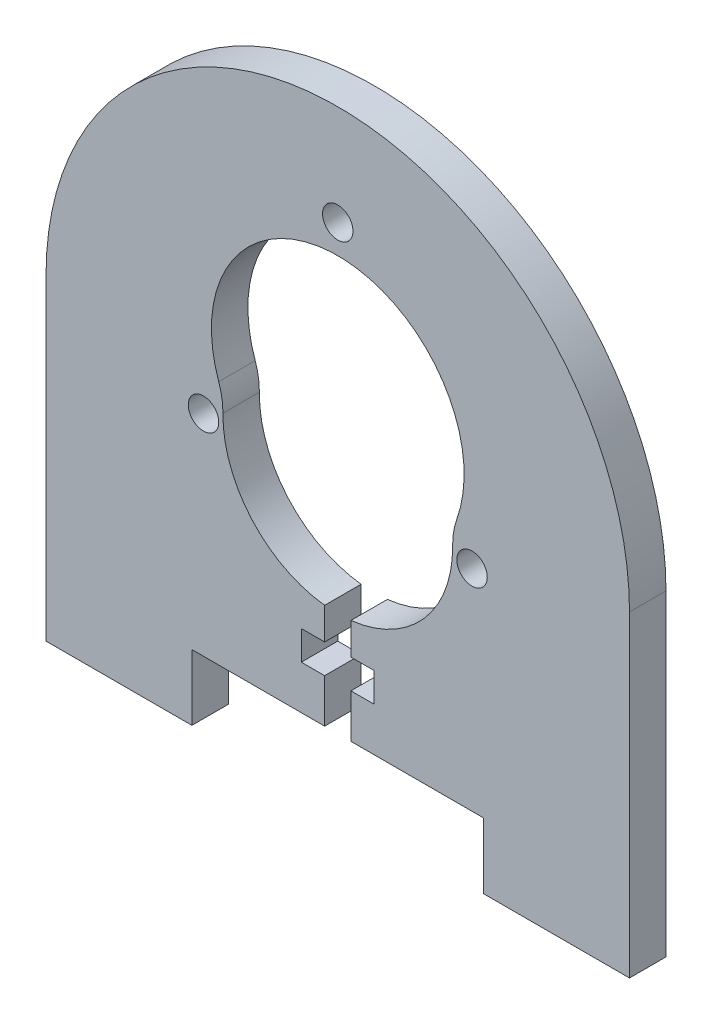
SolidWorks part; units mm, degrees
ref_plane "Front Plane" through (0, 0, 0) normal (0, 0, 1) x (1, 0, 0)
ref_plane "Top Plane" through (0, 0, 0) normal (0, 1, 0) x (1, 0, 0)
ref_plane "Right Plane" through (0, 0, 0) normal (1, 0, 0) x (0, 0, -1)
sketch "Sketch1" plane through (0, 0, 0) normal (0, 0, 1) x (1, 0, 0)
  line L0 (-25.4, 16.9649) -> (25.4, 16.9649) construction
  line L1 (25.4, -13.8001) -> (-25.4, -13.8001)
  line L2 (25.4, -13.8001) -> (25.4, 13.8001)
  line L3 (25.4, 13.8001) -> (-25.4, 13.8001) construction
  line L4 (-25.4, -13.8001) -> (-25.4, 13.8001)
  line L5 (25.4, -13.8001) -> (-25.4, 13.8001) construction
  line L6 (25.4, 13.8001) -> (-25.4, -13.8001) construction
  line L7 (0, 39.2001) -> (0, -13.8001) construction
  arc A0 (-25.4, 13.8001) -> (25.4, 13.8001) centre (0, 13.8001) cw
  circle A3 centre (0, 16.9649) radius 16.5 construction
  circle A4 centre (0, 22.9649) radius 2.5 construction
  point P0 (0, 0)
  dimension "D2" = 33
  dimension "D4" = 5
  dimension "D1" = 30.765
  dimension "D3" = 6
  dimension "D5" = 50.8
  dimension "D6" = 22.2352
extrude "Boss-Extrude1" add sketch "Sketch1" along normal blind 3.175
sketch "Sketch2" plane through (0, 0, 3.175) normal (0, 0, 1) x (1, 0, 0)
  circle A0 centre (0, 16.9649) radius 11
  dimension "D1" = 22
extrude "Cut-Extrude1" cut sketch "Sketch2" against normal up to next
sketch "Sketch3" plane through (0, 0, 3.175) normal (0, 0, 1) x (1, 0, 0)
  line L0 (25.4, -13.8001) -> (-25.4, -13.8001) construction
  line L1 (-12.7, -13.8001) -> (12.7, -13.8001)
  line L2 (-12.7, -13.8001) -> (-12.7, -8.0851)
  line L3 (-12.7, -8.0851) -> (12.7, -8.0851)
  line L4 (12.7, -13.8001) -> (12.7, -8.0851)
  line L6 (0, 39.2001) -> (0, -13.8001) construction
  point P6 (0, -8.0851)
  dimension "D1" = 5.715
  dimension "D2" = 25.4
extrude "Cut-Extrude2" cut sketch "Sketch3" against normal up to next
sketch "Sketch4" plane through (0, 0, 3.175) normal (0, 0, 1) x (1, 0, 0)
  line L0 (-25.4, -13.8001) -> (-12.7, -13.8001) construction
  line L1 (25.4, -13.8001) -> (-25.4, -13.8001) construction
  line L2 (-12.7, -8.0851) -> (-12.7, -13.8001) construction
  line L3 (-20.2866, -1014.3325) -> (-20.2866, 48985.6675) construction
  line L4 (0, -1.7463) -> (0, 1.7463) construction
  line L5 (-18.6991, 1.4399) -> (-21.8741, 1.4399)
  line L6 (-18.6991, 1.4399) -> (-18.6991, 7.7899)
  line L7 (-18.6991, 7.7899) -> (-21.8741, 7.7899)
  line L8 (-21.8741, 1.4399) -> (-21.8741, 7.7899)
  line L9 (-18.6991, 1.4399) -> (-21.8741, 7.7899) construction
  line L10 (-18.6991, 7.7899) -> (-21.8741, 1.4399) construction
  line L11 (18.6991, -1.1001) -> (21.8741, -7.4501) construction
  line L12 (-18.6991, -7.4501) -> (-21.8741, -7.4501)
  line L13 (-18.6991, -7.4501) -> (-18.6991, -1.1001)
  line L14 (-18.6991, -1.1001) -> (-21.8741, -1.1001)
  line L15 (-21.8741, -7.4501) -> (-21.8741, -1.1001)
  line L16 (-18.6991, -7.4501) -> (-21.8741, -1.1001) construction
  line L17 (-18.6991, -1.1001) -> (-21.8741, -7.4501) construction
  line L18 (18.6991, -7.4501) -> (21.8741, -1.1001) construction
  line L19 (18.6991, 7.7899) -> (21.8741, 1.4399) construction
  line L20 (18.6991, 1.4399) -> (21.8741, 7.7899) construction
  line L21 (21.8741, -7.4501) -> (21.8741, -1.1001)
  line L22 (18.6991, -1.1001) -> (21.8741, -1.1001)
  line L23 (18.6991, -7.4501) -> (18.6991, -1.1001)
  line L24 (18.6991, -7.4501) -> (21.8741, -7.4501)
  line L25 (21.8741, 1.4399) -> (21.8741, 7.7899)
  line L26 (18.6991, 7.7899) -> (21.8741, 7.7899)
  line L27 (18.6991, 1.4399) -> (18.6991, 7.7899)
  line L28 (18.6991, 1.4399) -> (21.8741, 1.4399)
  point P7 (-20.2866, -13.8001)
  point P9 (-20.2866, 4.6149)
  point P17 (-20.2866, -4.2751)
  point P23 (-19.05, -13.8001)
  point P35 (20.2866, -4.2751)
  point P36 (20.2866, 4.6149)
  dimension "D1" = 6.35
  dimension "D2" = 6.35
  dimension "D3" = 3.175
  dimension "D4" = 3.175
  dimension "D5" = 6.35
  dimension "D6" = 2.54
  dimension "D7" = 1.2366
extrude "Cut-Extrude3" [suppressed] cut sketch "Sketch4" against normal up to next
sketch "Sketch5" plane through (0, 0, 3.175) normal (0, 0, 1) x (1, 0, 0)
  line L0 (0, 39.2001) -> (0, -13.8001) construction
  line L1 (3.175, -4.2751) -> (1.143, -4.2751)
  line L2 (3.175, -4.2751) -> (3.175, -1.7351)
  line L3 (3.175, -1.7351) -> (1.143, -1.7351)
  line L4 (-3.175, -4.2751) -> (-3.175, -1.7351)
  line L5 (3.175, -4.2751) -> (-3.175, -1.7351) construction
  line L6 (3.175, -1.7351) -> (-3.175, -4.2751) construction
  line L7 (12.7, -8.0851) -> (-12.7, -8.0851) construction
  line L8 (-1.143, -1.7351) -> (-3.175, -1.7351)
  line L9 (-1.143, -8.0851) -> (1.143, -8.0851)
  line L10 (-1.143, -8.0851) -> (-1.143, -4.2751)
  line L11 (-1.143, 7.1549) -> (1.143, 7.1549)
  line L12 (1.143, -8.0851) -> (1.143, -4.2751)
  line L13 (-1.143, -1.7351) -> (-1.143, 7.1549)
  line L14 (1.143, -1.7351) -> (1.143, 7.1549)
  line L15 (-1.143, -4.2751) -> (-3.175, -4.2751)
  point P0 (0, -3.0051)
  point P14 (0, 7.1549)
  dimension "D1" = 6.35
  dimension "D2" = 2.54
  dimension "D3" = 3.81
  dimension "D4" = 2.286
  dimension "D5" = 15.24
extrude "Cut-Extrude4" cut sketch "Sketch5" against normal up to next
sketch "Sketch6" plane through (0, 0, 0) normal (0, 0, 1) x (1, 0, 0)
  line L0 (0, 39.2001) -> (0, -13.8001) construction
  circle A0 centre (0, 30.4649) radius 1.325
  circle A1 centre (11.6913, 10.2149) radius 1.325
  circle A2 centre (-11.6913, 10.2149) radius 1.325
  point P10 (0, 16.9649)
  dimension "D1" = 2.65
  dimension "D3" = 13.5
  dimension "D2" = 3
extrude "Cut-Extrude6" cut sketch "Sketch6" along normal through all
sketch "Sketch7" plane through (0, 0, 0) normal (0, 0, 1) x (1, 0, 0)
  line L0 (0, 39.2001) -> (0, -13.8001) construction
  circle A0 centre (0, 10.9649) radius 10
  dimension "D1" = 20
  dimension "D2" = 6
extrude "Cut-Extrude7" cut sketch "Sketch7" along normal through all
fillet "Fillet1" radius 6.35 2 edges at (-9.9216, 12.2149, 1.5875) (9.9216, 12.2149, 1.5875)
equation "\"D2@Sketch1\"=33mm"
equation "\"D1@Sketch1\"=0.75+\"thickness0.25\"+\"motor offset\""
equation "\"t\"=0.125"
equation "\"D1@Boss-Extrude1\"=\"t\""
equation "\"D4@Sketch4\"=\"t\""
equation "\"D3@Sketch4\"=\"t\""
equation "\"motor offset\"= 6mm"
equation "\"thickness0.25\"= 0.225in"
equation "\"thickness0.125\"= 0.122in"
equation "\"motor diameter\"= 33mm"
equation "\"D3@Sketch1\"=\"motor offset\""
equation "\"D1@Sketch3\"=\"thickness0.25\""
equation "\"D2@Sketch7\"=\"motor offset\""
